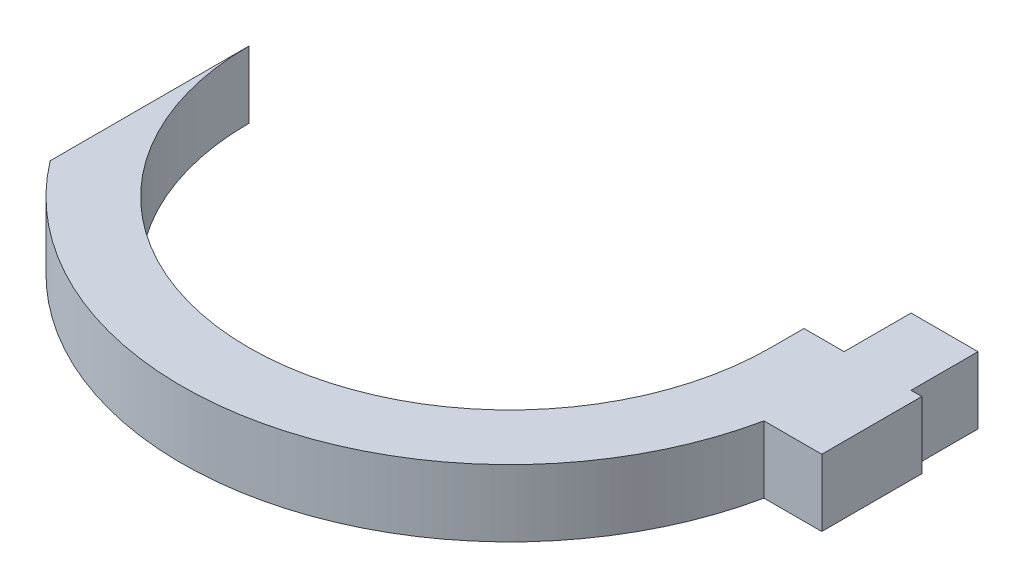
SolidWorks part; units mm, degrees
ref_plane "Front Plane" through (0, 0, 0) normal (0, 0, 1) x (1, 0, 0)
ref_plane "Top Plane" through (0, 0, 0) normal (0, 1, 0) x (1, 0, 0)
ref_plane "Right Plane" through (0, 0, 0) normal (1, 0, 0) x (0, 0, -1)
sketch "Sketch1" plane through (0, 0, 0) normal (0, 1, 0) x (1, 0, 0)
  line L0 (53.34, 3.1377) -> (53.34, 9.4877)
  line L1 (53.34, 9.4877) -> (59.69, 9.4877)
  line L2 (59.69, 9.4877) -> (59.69, 3.1377)
  line L3 (49.53, 0) -> (49.53, 3.1377)
  line L4 (0, 0) -> (0, -18.8371)
  line L5 (49.53, 3.1377) -> (53.34, 3.1377)
  line L6 (60.706, 0) -> (60.706, -6.35)
  line L7 (60.706, -6.35) -> (55.2251, -6.35)
  line L8 (60.706, 0) -> (60.706, 3.1377)
  line L9 (60.706, 3.1377) -> (59.69, 3.1377)
  arc A0 (49.53, 0) -> (0, 0) centre (24.765, 0) cw
  arc A1 (0, -18.8371) -> (55.2251, -6.35) centre (24.765, 0) ccw
  dimension "D1" = 24.765
  dimension "D5" = 6.35
  dimension "D4" = 6.35
  dimension "D2" = 3.81
  dimension "D3" = 6.35
  dimension "D6" = 3.1377
  dimension "D7" = 1.016
extrude "Boss-Extrude1" add sketch "Sketch1" along normal blind 6.35
equation "\"Ball Diameter\"= 1.75in"
equation "\"Sheet Thickness\"= 0.25in"
equation "\"Screw Diameter\"= .17in"
equation "\"Robot Diameter\"= 14in"
equation "\"Castor Screw Diameter\"= 0.22in"
equation "\"Wheel Diameter\" = 4in"
equation "\"Nut Diameter\" = 8.4mm"
equation "\"Nut Height\" = 2.9mm"
equation "\"Screw Height\" = 0.55in"
equation "\"Pulley Diameter\" = 1in"
equation "\"Reactor Height\" = 14in"
equation "\"Elevator Height\" = 11.5in"
equation "\"Elevator Width\" = \"Ball Diameter\" + 0.25in"
equation "\"Elevator Bearing Diameter\" = sqr(2*(\"Sheet Thickness\"^2)) + 0.2in"
equation "\"Elevator Axle Endcap Diameter\" = \"Pulley Diameter\" + 0.25in"
equation "\"Elevator Axle Length\" = \"Elevator Width\" + 8*\"Sheet Thickness\""
equation "\"Elevator Clearance from Axis\" = (\"Pulley Diameter\"/2) + \"Ball Diameter\" + 0.5in"
equation "\"D1@Sketch1\"=\"Claw Radius\""
equation "\"D3@Sketch1\"=\"Sheet Thickness\""
equation "\"D4@Sketch1\"=\"Sheet Thickness\""
equation "\"D5@Sketch1\"=\"Sheet Thickness\""
equation "\"D1@Boss-Extrude1\"=\"Sheet Thickness\""
equation "\"D6@Sketch1\"=(\"Claw Radius\")*(1 -  sin(arccos((\"Claw Horizontal Seperation\"/\"Claw Radius\"))))"
equation "\"Claw Horizontal Seperation\" = (\"Elevator Width\"/2) - (1.5 * \"Sheet Thickness\") - 0.15in"
equation "\"Ball Radius\" = \"Ball Diameter\"/2"
equation "\"Claw Radius\" = \"Ball Radius\" + 0.1in"
